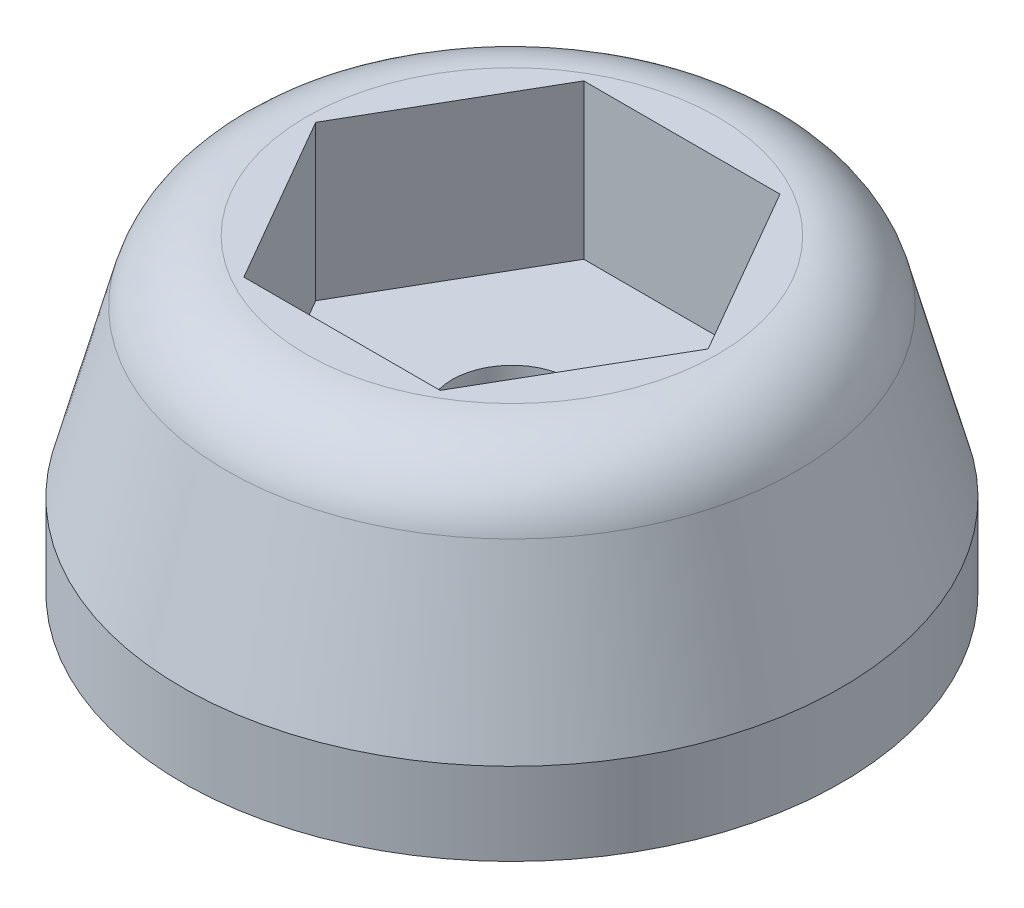
SolidWorks part; units mm, degrees
ref_plane "Front" through (0, 0, 0) normal (0, 0, 1) x (1, 0, 0)
ref_plane "Top" through (0, 0, 0) normal (0, 1, 0) x (1, 0, 0)
ref_plane "Right" through (0, 0, 0) normal (1, 0, 0) x (0, 0, -1)
ref_axis "side-side" through (80.9, 0, 0) along (-1, 0, 0)
ref_axis "up-down" through (0, 50, 0) along (0, -1, 0)
ref_axis "front-back" through (0, 0, -80.9) along (0, 0, 1)
sketch "Sketch1" plane through (0, 0, 0) normal (0, 0, 1) x (1, 0, 0)
  line L0 (0, 0) -> (0, -22.0589) construction
  line L1 (-1.4732, 0) -> (-8.128, 0)
  line L2 (-1.4732, 0) -> (-1.4732, 7.62)
  line L3 (-1.4732, 7.62) -> (-5.0715, 7.62)
  line L4 (-8.128, 0) -> (-8.128, 2.032)
  line L5 (-8.128, 2.032) -> (-7.0343, 6.1139)
  line L6 (-5.1617, 2.032) -> (-6.0243, 2.032) construction
  line L7 (-6.0243, 2.032) -> (-5.0715, 5.588) construction
  line L8 (-5.0715, 5.588) -> (-5.588, 5.588) construction
  line L9 (-5.588, 5.588) -> (-5.588, 2.54) construction
  line L10 (-5.588, 2.54) -> (-3.5052, 2.54) construction
  line L11 (-3.5052, 2.54) -> (-3.5052, 2.032) construction
  line L12 (-1.4732, 2.032) -> (-8.128, 2.032) construction
  line L13 (-5.588, 2.54) -> (-5.1617, 2.032) construction
  arc A0 (-7.0343, 6.1139) -> (-5.0715, 7.62) centre (-5.0715, 5.588) cw
  point P9 (-5.5479, 3.81)
  dimension "D1" = 2.032
  dimension "D2" = 15
  dimension "D3" = 16.256
  dimension "D4" = 7.62
  dimension "D5" = 2.032
  dimension "D6" = 2.9464
  dimension "D8" = 5.588
  dimension "D9" = 5.08
  dimension "D10" = 2.032
  dimension "D11" = 2.032
  dimension "D12" = 2.032
  dimension "D13" = 50
  dimension "D7" = 2.032
revolve "Revolve1" add sketch "Sketch1" angle 360 about L0
sketch "Sketch2" plane through (0, 7.62, 0) normal (0, 1, 0) x (1, 0, 0)
  line L1 (-4.8393, 0) -> (-2.4197, -4.191)
  line L2 (-2.4197, -4.191) -> (2.4197, -4.191)
  line L3 (2.4197, -4.191) -> (4.8393, 0)
  line L4 (4.8393, 0) -> (2.4197, 4.191)
  line L5 (2.4197, 4.191) -> (-2.4197, 4.191)
  line L6 (-2.4197, 4.191) -> (-4.8393, 0)
  circle A0 centre (0, 0) radius 4.191 construction
  dimension "D1" = 8.382
extrude "Cut-Extrude1" cut sketch "Sketch2" against normal blind 3.81
